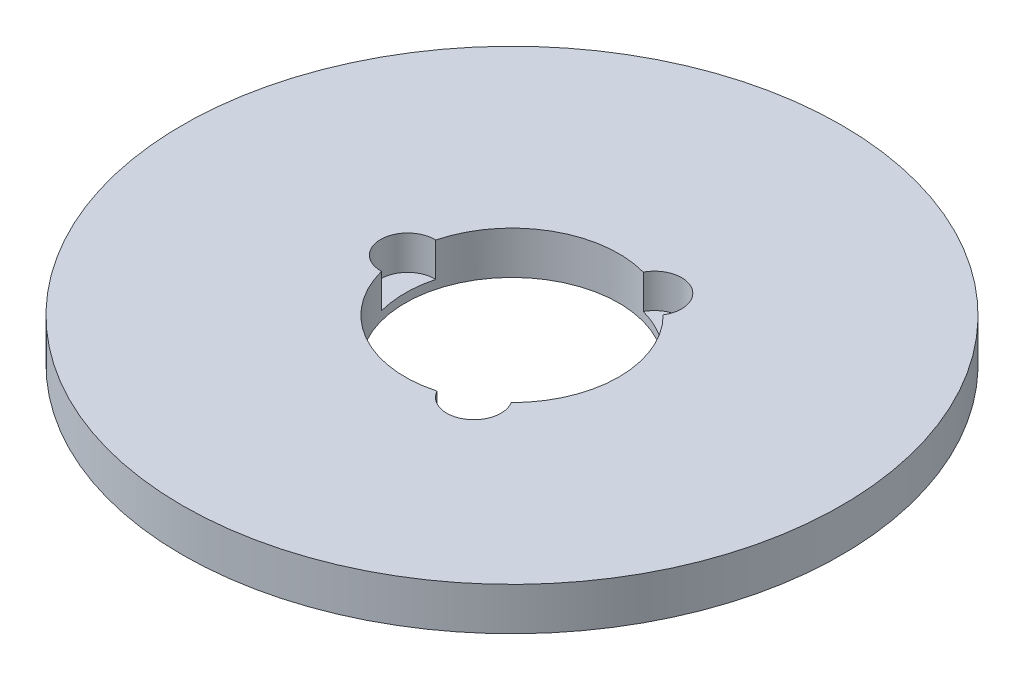
SolidWorks part; units mm, degrees
ref_plane "Front Plane" through (0, 0, 0) normal (0, 0, 1) x (1, 0, 0)
ref_plane "Top Plane" through (0, 0, 0) normal (0, 1, 0) x (1, 0, 0)
ref_plane "Right Plane" through (0, 0, 0) normal (1, 0, 0) x (0, 0, -1)
sketch "Sketch1" plane through (0, 0, 0) normal (0, 1, 0) x (1, 0, 0)
  circle A0 centre (0, 0) radius 92.5
  dimension "FLANGE_OD" = 185
extrude "Boss-Extrude1" add sketch "Sketch1" along normal blind 12
sketch "Sketch2" plane through (0, 0, 0) normal (0, 1, 0) x (1, 0, 0)
  circle A0 centre (0, 0) radius 30
  dimension "BORE_D" = 60
extrude "Cut-Extrude1" cut sketch "Sketch2" along normal through all
sketch "Sketch3" plane through (0, 12, 0) normal (0, 1, 0) x (1, 0, 0)
  circle A0 centre (0, 0) radius 29.2726 construction
  circle A1 centre (-29.2726, 0) radius 7.6144
  dimension "BOLT_D" = 15.2288
  dimension "BOLT_PCD" = 58.5452
extrude "Cut-Extrude2" cut sketch "Sketch3" against normal blind 9.5827
pattern_circular "CirPattern1" count 3 over 360 about axis through (0, 0, 0) along (0, 1, 0) of "Cut-Extrude2"
